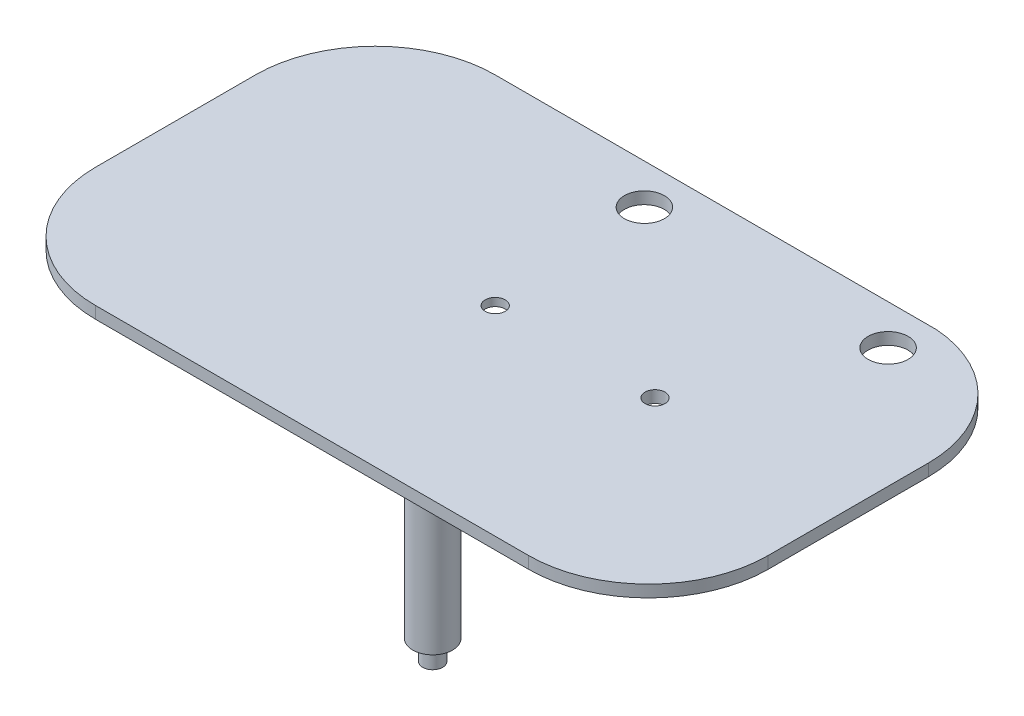
SolidWorks part; units mm, degrees
ref_plane "前视基准面" through (0, 0, 0) normal (0, 0, 1) x (1, 0, 0)
ref_plane "上视基准面" through (0, 0, 0) normal (0, 1, 0) x (1, 0, 0)
ref_plane "右视基准面" through (0, 0, 0) normal (1, 0, 0) x (0, 0, -1)
other "Configuration Table"
sketch "草图1" plane through (0, 0, 0) normal (0, 1, 0) x (1, 0, 0)
  line L0 (50, 0) -> (50, 85.1816) construction
  line L1 (0, 0) -> (100, 0)
  line L2 (0, 0) -> (0, -100)
  line L3 (0, -100) -> (100, -100)
  line L4 (100, 0) -> (100, -100)
  line L5 (9.5, 75.0478) -> (9.5, 17.1128) construction
  line L6 (90.5, 75.0478) -> (90.5, 17.1128) construction
  line L7 (-7.6482, 80) -> (134.4168, 80) construction
  line L8 (0, 0) -> (9.5, 12.5)
  line L9 (100, 0) -> (90.5, 12.5)
  line L10 (90.5, 12.5) -> (90.5, 212.5)
  line L11 (90.5, 212.5) -> (9.5, 212.5)
  line L12 (9.5, 212.5) -> (9.5, 12.5)
  line L13 (90.5, 12.5) -> (90.5, 0)
  line L14 (9.5, 12.5) -> (9.5, 0)
  dimension "D1" = 100
  dimension "D2" = 100
  dimension "D3" = 81
  dimension "D4" = 80
  dimension "D5" = 200
extrude "凸台-拉伸1" add sketch "草图1" along normal blind 50 and the other way blind 50 contours L12 L14 L1 L13 L10 L11 region at (50, 0, -106.25)
ref_plane "基准面1" through (0, 0, 0) normal (0, -1, 0) x (-1, 0, 0)
sketch "草图2" plane through (0, 0, 0) normal (0, -1, 0) x (-1, 0, 0)
  line L0 (-130.3132, 0) -> (40.2206, 0) construction
  line L1 (-150, 0) -> (-150, -100)
  line L2 (-150, -100) -> (50, -100)
  line L3 (50, -100) -> (50, 0)
  line L4 (50, 0) -> (-150, 0)
  line L5 (-50, 212.5) -> (-50, 195.989) construction
  line L6 (-90.5, 212.5) -> (-9.5, 212.5) construction
  point P10 (-50, 212.5)
  dimension "D1" = 200
  dimension "D2" = 100
extrude "凸台-拉伸2" add sketch "草图2" against normal blind 40
ref_plane "基准面2" through (0, 0, 100) normal (0, 0, 1) x (1, 0, 0)
sketch "草图3" plane through (0, 0, 100) normal (0, 0, 1) x (1, 0, 0)
  line L0 (-50, 37) -> (150, 37)
  line L1 (-50, 40) -> (-50, 0) construction
  line L2 (150, 40) -> (150, 0) construction
  line L3 (150, 37) -> (150, 3)
  line L4 (150, 3) -> (-50, 3)
  line L5 (-50, 3) -> (-50, 37)
  line L6 (150, 0) -> (-50, 0) construction
  line L7 (150, 40) -> (-50, 40) construction
  dimension "D1" = 3
  dimension "D2" = 3
extrude "切除-拉伸1" cut sketch "草图3" against normal blind 100
ref_plane "基准面3" through (34.5, 0, 0) normal (-1, 0, 0) x (0, 0, 1)
ref_plane "基准面4" through (0, 50, 0) normal (0, 1, 0) x (1, 0, 0)
sketch "草图6" plane through (0, 50, 0) normal (0, 1, 0) x (1, 0, 0)
  line L0 (12.5, 212.5) -> (12.5, 5)
  line L1 (90.5, 212.5) -> (9.5, 212.5) construction
  line L2 (12.5, 5) -> (87.5, 5)
  line L3 (87.5, 5) -> (87.5, 212.5)
  line L4 (9.5, 212.5) -> (9.5, 0) construction
  line L5 (90.5, 212.5) -> (90.5, 0) construction
  line L7 (9.5, 0) -> (90.5, 0) construction
  dimension "D1" = 3
  dimension "D2" = 3
  dimension "D3" = 5
extrude "切除-拉伸2" cut sketch "草图6" against normal through all
ref_plane "基准面5" through (0, 40, 0) normal (0, 1, 0) x (1, 0, 0)
sketch "草图8" plane through (0, 40, 0) normal (0, 1, 0) x (1, 0, 0)
  line L0 (-50, -50) -> (102.2011, -50) construction
  line L1 (-50, -100) -> (-50, 0) construction
  line L2 (50, 0) -> (50, -100) construction
  line L3 (9.5, 0) -> (90.5, 0) construction
  line L4 (-22, -100) -> (22, -100) construction
  circle A0 centre (70, -50) radius 2.5
  circle A1 centre (30, -50) radius 2.5
  dimension "D1" = 5
  dimension "D2" = 5
  dimension "D3" = 40
extrude "切除-拉伸4" cut sketch "草图8" against normal through all
ref_plane "基准面6" through (90.5, 0, 0) normal (1, 0, 0) x (0, 0, -1)
sketch "草图10" plane through (90.5, 0, 0) normal (1, 0, 0) x (0, 0, -1)
  line L0 (39.5916, 0) -> (155.7144, 0) construction
  line L2 (0, 37) -> (0, 3) construction
  circle A0 centre (80, 0) radius 5
  circle A1 centre (180, 0) radius 5
  dimension "D3" = 10
  dimension "D4" = 10
  dimension "D1" = 80
  dimension "D2" = 180
extrude "切除-拉伸5" cut sketch "草图10" against normal through all
sketch "草图11" plane through (9.5, 0, 0) normal (-1, 0, 0) x (0, 0, 1)
  line L2 (-30.9056, 83.4152) -> (-74.0944, 50)
  line L3 (44.55, 50) -> (-44.55, 50) construction
  line L4 (-74.0944, 50) -> (0, 50)
  line L5 (0, 40) -> (0, 50) construction
  line L6 (0, 50) -> (0, 40)
  line L8 (-30.9056, 83.4152) -> (83.321, 40)
  line L9 (100, 40) -> (0, 40) construction
  line L10 (83.321, 40) -> (0, 40)
extrude "凸台-拉伸5" add sketch "草图11" against normal blind 10
sketch "草图13" plane through (90.5, 0, 0) normal (1, 0, 0) x (0, 0, -1)
  line L0 (0, 36.2107) -> (0, 62.8442) construction
  line L1 (44.55, 50) -> (-44.55, 50) construction
  line L2 (74.1158, 50) -> (0, 50)
  line L3 (74.1158, 50) -> (74.1158, 53)
  line L4 (74.1158, 53) -> (0, 53)
  line L5 (0, 50) -> (0, 53)
  dimension "D1" = 3
extrude "凸台-拉伸7" add sketch "草图13" against normal blind 81
ref_plane "基准面7" through (12.5, 0, 0) normal (1, 0, 0) x (0, 0, -1)
sketch "草图14" plane through (12.5, 0, 0) normal (1, 0, 0) x (0, 0, -1)
  line L0 (5, -46.5508) -> (5, 34.4221) construction
  line L2 (5, -50) -> (212.5, -50)
  line L3 (212.5, -50) -> (212.5, 50)
  line L4 (44.55, 50) -> (-44.55, 50) construction
  line L5 (212.5, -50) -> (212.5, 50) construction
  line L6 (212.5, 50) -> (5, 50)
  line L7 (5, 50) -> (5, -50)
extrude "凸台-拉伸8" add sketch "草图14" along normal blind 7
sketch "草图15" plane through (90.5, 0, 0) normal (1, 0, 0) x (0, 0, -1)
  line L0 (30.9056, 83.4152) -> (-82.9022, 40)
  line L1 (55, 40) -> (-55, 40) construction
  line L2 (-82.9022, 40) -> (0, 40)
  line L3 (0, 37) -> (0, 40) construction
  line L4 (0, 40) -> (0, 53)
  line L5 (0, 53) -> (70.217, 53)
  line L6 (70.217, 53) -> (30.9056, 83.4152)
extrude "凸台-拉伸9" add sketch "草图15" against normal blind 10
ref_plane "基准面8" through (0, 37, 0) normal (0, -1, 0) x (-1, 0, 0)
ref_plane "基准面9" through (0, 3, 0) normal (0, 1, 0) x (1, 0, 0)
sketch "草图17" plane through (0, 37, 0) normal (0, -1, 0) x (-1, 0, 0)
  circle A0 centre (-30, -50) radius 6.35
  dimension "D1" = 12.7
extrude "切除-拉伸6" cut sketch "草图17" against normal blind 1
sketch "草图18" plane through (0, 3, 0) normal (0, 1, 0) x (1, 0, 0)
  circle A0 centre (30, -50) radius 6.35
  dimension "D1" = 12.7
extrude "切除-拉伸7" cut sketch "草图18" against normal blind 1
sketch "草图20" plane through (0, 0, 0) normal (0, -1, 0) x (1, 0, 0)
  line L0 (7.57, 50) -> (34.6356, 50) construction
  line L1 (30, 52.5) -> (30, 68.4286) construction
  circle A1 centre (-31.25, 50) radius 5
  circle A2 centre (91.25, 50) radius 5
  dimension "D2" = 10
  dimension "D4" = 10
  dimension "D1" = 61.25
  dimension "D3" = 61.25
extrude "切除-拉伸8" cut sketch "草图20" against normal blind 3
cosmetic thread "装饰螺纹线1" parameters "D2"=11
cosmetic thread "装饰螺纹线2" parameters "D2"=11
sketch "草图21" plane through (0, 3, 0) normal (0, 1, 0) x (1, 0, 0)
  line L0 (118.3346, -100) -> (118.3346, 0)
  line L1 (-22, -100) -> (22, -100) construction
  line L2 (90.5, 0) -> (150, 0) construction
  line L3 (118.3346, 0) -> (150, 0)
  line L4 (150, 0) -> (150, -100)
  line L5 (150, 0) -> (150, -100) construction
  line L6 (150, -100) -> (118.3346, -100)
extrude "切除-拉伸9" cut sketch "草图21" along normal through all both and the other way through all
sketch "草图22" plane through (0, 0, 0) normal (0, -1, 0) x (1, 0, 0)
  line L0 (-38.0419, 14.9384) -> (110.8032, 14.9384) construction
  circle A0 centre (-28.835, 14.9384) radius 5
  circle A1 centre (99.9437, 14.9384) radius 5
  circle A2 centre (47.3586, 88.9028) radius 5
  dimension "D1" = 10
  dimension "D2" = 10
  dimension "D3" = 10
extrude "凸台-拉伸10" add sketch "草图22" against normal up to surface (37 mm away) up to face at (70, 37, 52.5)
fillet "圆角1" radius 30 10 edges at (14.5, 83.4152, -30.9056) (85.5, 83.4152, -30.9056) (118.3346, 38.5, 0) (118.3346, 1.5, 0) (118.3346, 38.5, 100) (118.3346, 1.5, 100) (-50, 38.5, 100) (-50, 38.5, 0) (-50, 1.5, 0) (-50, 1.5, 100)
fillet "圆角2" radius 30 2 edges at (89, -50, -212.5) (89, 50, -212.5)
sketch "草图23" plane through (19.5, 0, 0) normal (1, 0, 0) x (0, 0, -1)
  line L0 (-82.9022, 40) -> (15.1729, 77.4135)
  line L1 (55, 40) -> (-55, 40) construction
  line L2 (15.1729, 77.4135) -> (-82.9022, 40) construction
  line L3 (15.1729, 77.4135) -> (30.2606, 83.1692)
  line L4 (30.2606, 83.1692) -> (82.9117, 53.4848)
  line L5 (82.9117, 53.4848) -> (216.9824, 51.4008)
  line L6 (216.9824, 51.4008) -> (216.9824, -53.0307)
  line L7 (216.9824, -53.0307) -> (0, -55.3463)
  line L8 (0, -55.3463) -> (0, 40)
  line L9 (0, 40) -> (-82.9022, 40)
  arc A0 (44.2235, 73.1112) -> (15.1729, 77.4135) centre (25.8656, 49.3838) ccw construction
extrude "切除-拉伸10" cut sketch "草图23" against normal through all both and the other way through all
ref_plane "基准面10" through (0, 0, 0) normal (0, -1, 0) x (-1, 0, 0)
sketch "草图24" plane through (0, 0, 0) normal (0, -1, 0) x (1, 0, 0)
  line L0 (-36.25, 50) -> (-26.25, 50) construction
  line L1 (-50, 66.8294) -> (-50, 70)
  line L2 (-50, 70) -> (-50, 30) construction
  line L3 (1.65, 100) -> (-1.65, 100) construction
  line L4 (-20, 100) -> (88.3346, 100)
  line L5 (118.3346, 70) -> (118.3346, 30)
  line L6 (88.3346, 0) -> (-20, 0)
  line L7 (-50, 0) -> (-50, 30)
  line L8 (-50, 30) -> (-50, 66.8294)
  line L9 (-20, 0) -> (90.5, 0) construction
  line L10 (118.3346, 29.9218) -> (118.3346, 70) construction
  circle A0 centre (-31.25, 50) radius 5 construction
  circle A1 centre (-31.25, 50) radius 5
  circle A2 centre (30, 50) radius 2.5
  circle A3 centre (70, 50) radius 2.5
  circle A4 centre (91.25, 50) radius 5
  arc A6 (118.3346, 70) -> (88.3346, 100) centre (88.3346, 70) ccw
  arc A7 (-50, 70) -> (-20, 100) centre (-20, 70) cw
  arc A8 (88.3346, 0) -> (118.3346, 30) centre (88.3346, 30) ccw
  arc A9 (-20, 0) -> (-50, 30) centre (-20, 30) cw
  point P35 (118.3346, 100)
  point P38 (-50, 100)
  dimension "D1" = 30
  dimension "D2" = 30
  dimension "D3" = 30
  dimension "D4" = 30
sketch "草图25" plane through (118.3346, 0, 0) normal (1, 0, 0) x (0, 0, -1)
  line L0 (-96.9992, 37) -> (-5.7141, 37)
  line L1 (-100, 37) -> (-70, 37) construction
  line L2 (-29.9218, 37) -> (0, 37) construction
  line L3 (-5.7141, 37) -> (-5.7141, 3)
  line L4 (55, 3) -> (-55, 3) construction
  line L5 (-5.7141, 3) -> (-98.6224, 3)
  line L6 (-98.6224, 3) -> (-96.9992, 37)
extrude "切除-拉伸11" cut sketch "草图25" against normal through all both and the other way through all
sketch "草图26" plane through (0, 0, 0) normal (0, -1, 0) x (1, 0, 0)
  line L1 (88.3346, 0) -> (88.3346, 38.8394) construction
  line L2 (27.3346, 31.1143) -> (27.3346, -2.0928) construction
  circle A1 centre (88.3346, 10) radius 5
  circle A2 centre (27.3346, 10) radius 5
  dimension "D1" = 10
  dimension "D4" = 10
  dimension "D2" = 10
  dimension "D3" = 61
extrude "切除-拉伸12" cut sketch "草图26" against normal through all both and the other way through all
sketch "草图27" plane through (34.5, 0, 0) normal (-1, 0, 0) x (0, 0, 1)
  line L0 (-18.9418, 81.6961) -> (-17.6639, 66.3073)
  line L1 (-17.6639, 66.3073) -> (80.7391, 40)
  line L2 (100, 40) -> (70, 40) construction
  line L3 (80.7391, 40) -> (87.3419, 40)
  line L4 (87.3419, 40) -> (-18.9418, 81.6961)
extrude "切除-拉伸13" cut sketch "草图27" against normal through all both and the other way through all
sketch "草图30" plane through (0, 37, 0) normal (0, -1, 0) x (1, 0, 0)
  circle A0 centre (88.3346, 10) radius 7.5
  dimension "D1" = 15
extrude "切除-拉伸14" cut sketch "草图30" against normal through all both and the other way through all
sketch "草图31" plane through (0, 37, 0) normal (0, -1, 0) x (1, 0, 0)
  circle A0 centre (27.3346, 10) radius 7.5
  circle A1 centre (27.3346, 10) radius 5
  dimension "D1" = 15
extrude "切除-拉伸15" cut sketch "草图31" against normal through all both and the other way through all
sketch "草图32" plane through (0, 0, 0) normal (0, -1, 0) x (1, 0, 0)
  circle A0 centre (27.3346, 10) radius 5
  circle A1 centre (27.3346, 10) radius 7.5
  dimension "D1" = 10
extrude "凸台-拉伸12" add sketch "草图32" against normal blind 3
sketch "草图33" plane through (0, 0, 0) normal (0, -1, 0) x (1, 0, 0)
  circle A0 centre (88.3346, 10) radius 5
  circle A1 centre (88.3346, 10) radius 7.5
  dimension "D1" = 10
  dimension "D2" = 15
extrude "凸台-拉伸13" add sketch "草图33" against normal blind 3
sketch "草图34" plane through (0, 37, 0) normal (0, -1, 0) x (1, 0, 0)
  line L0 (27.3346, 10) -> (27.3346, 28.3647) construction
  line L1 (87.8566, 10) -> (87.8566, 33.5037) construction
  line L2 (57.3566, 24.8807) -> (57.3566, 51.8819) construction
  circle A0 centre (57.3566, 86.5535) radius 5
  dimension "D2" = 10
  dimension "D1" = 30.5
extrude "凸台-拉伸14" add sketch "草图34" along normal blind 45
sketch "草图36" plane through (0, -8, 0) normal (0, -1, 0) x (1, 0, 0)
  circle A0 centre (57.3566, 86.5535) radius 2.5
  dimension "D1" = 5
sketch "草图37" plane through (90.5, 0, 0) normal (1, 0, 0) x (0, 0, -1)
  line L0 (-55, 37) -> (55, 37) construction
  line L1 (4.4317, 37) -> (-127.7754, 37)
  line L2 (4.4317, 37) -> (4.4317, -30.7537)
  line L3 (4.4317, -30.7537) -> (-127.7754, -30.7537)
  line L4 (-127.7754, 37) -> (-127.7754, -30.7537)
extrude "切除-拉伸17" cut sketch "草图37" against normal through all both and the other way through all
sketch "草图41" plane through (0, 37, 0) normal (0, -1, 0) x (1, 0, 0)
  circle A0 centre (27.3346, 10) radius 5
  circle A1 centre (27.3346, 10) radius 7.5
  dimension "D1" = 10
sketch "草图43" plane through (0, 37, 0) normal (0, -1, 0) x (1, 0, 0)
  line L0 (57.3566, 86.5535) -> (57.3566, 100)
  line L1 (-20, 100) -> (88.3346, 100) construction
  circle A0 centre (57.3566, 93) radius 5
  dimension "D1" = 10
  dimension "D2" = 7
extrude "凸台-拉伸19" add sketch "草图43" along normal blind 34 contours L0 A0 | L0 A0 region at (55.2345, 37, 93) region at (59.4787, 37, 93)
sketch "草图44" plane through (0, 3, 0) normal (0, -1, 0) x (1, 0, 0)
  circle A0 centre (57.3566, 93) radius 2.5
  dimension "D1" = 5
extrude "凸台-拉伸20" add sketch "草图44" along normal blind 5
extrude "凸台-拉伸17" add sketch "草图41" against normal blind 3
sketch "草图42" plane through (0, 37, 0) normal (0, -1, 0) x (1, 0, 0)
  circle A0 centre (88.3346, 10) radius 7.5
  circle A1 centre (88.3346, 10) radius 5
  dimension "D1" = 10
extrude "凸台-拉伸18" add sketch "草图42" against normal blind 3
sketch "草图45" plane through (0, 37, 0) normal (0, -1, 0) x (1, 0, 0)
  line L0 (-20, 0) -> (-20, 39.7566) construction
  line L1 (-20, 15) -> (117.2222, 15) construction
  line L2 (88.3346, 10) -> (88.3346, 21.125) construction
  circle A0 centre (-20, 15) radius 5
  circle A1 centre (100.3346, 15) radius 5
  dimension "D1" = 10
  dimension "D3" = 10
  dimension "D2" = 15
  dimension "D4" = 12
